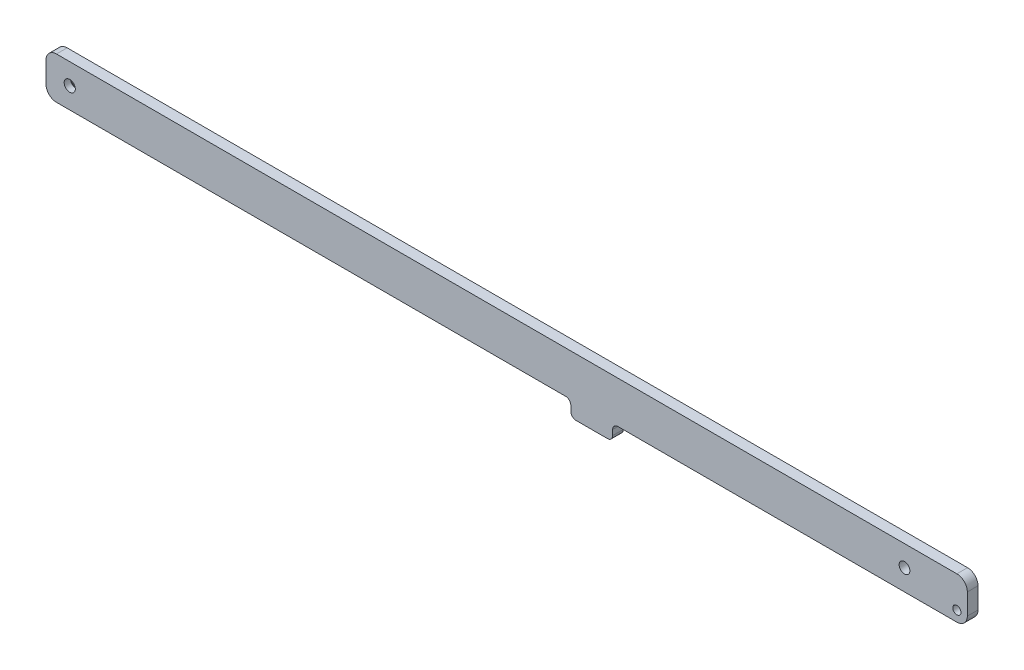
SolidWorks part; units mm, degrees
material "PC High Viscosity"
ref_plane "Front Plane" through (0, 0, 0) normal (0, 0, 1) x (1, 0, 0)
ref_plane "Top Plane" through (0, 0, 0) normal (0, 1, 0) x (1, 0, 0)
ref_plane "Right Plane" through (0, 0, 0) normal (1, 0, 0) x (0, 0, -1)
sketch "Sketch1" plane through (0, 0, 0) normal (0, 0, 1) x (1, 0, 0)
  line L1 (0, 0) -> (40.5308, 0)
  line L2 (0, 0) -> (0, 25.4)
  line L3 (0, 25.4) -> (40.5307, 25.4)
  line L4 (558.8, 0) -> (558.8, 25.4)
  line L11 (558.8, 10.0162) -> (552.45, 13.6823) construction
  line L12 (552.45, 13.6823) -> (546.1, 10.0162) construction
  line L13 (546.1, 10.0162) -> (546.1, 2.6838) construction
  line L14 (546.1, 2.6838) -> (552.45, -0.9823) construction
  line L15 (552.45, -0.9823) -> (558.8, 2.6838) construction
  line L16 (558.8, 2.6838) -> (558.8, 10.0162) construction
  line L19 (318.3103, 0) -> (318.3103, -9.525)
  line L20 (318.3103, -9.525) -> (343.7103, -9.525)
  line L21 (343.7103, -9.525) -> (343.7103, 0)
  line L22 (40.5307, 25.4) -> (558.8, 25.4)
  line L23 (40.5308, 0) -> (318.3103, 0)
  line L24 (343.7103, 0) -> (558.8, 0)
  circle A0 centre (552.45, 6.35) radius 2.4892
  circle A1 centre (552.45, 6.35) radius 6.35 construction
  dimension "D5" = 4.9784
  dimension "D7" = 12.7
  dimension "D1" = 558.8
  dimension "D2" = 25.4
  dimension "D3" = 9.525
  dimension "D4" = 318.3103
  dimension "D9" = 25.4
extrude "Boss-Extrude1" add sketch "Sketch1" along normal blind 6.477 contours L3 | L1 L4 L3 L2 A0 | L1 region at (279.8974, 12.4155, 0)
fillet "Fillet2" radius 6.35 4 edges at (558.8, 25.4, 3.2385) (0, 0, 3.2385) (0, 25.4, 3.2385) (558.8, 0, 3.2385)
sketch "Sketch2" plane through (0, 0, 6.477) normal (0, 0, 1) x (1, 0, 0)
  line L2 (558.8, 6.35) -> (558.8, 19.05) construction
  line L3 (6.35, 25.4) -> (552.45, 25.4) construction
  circle A0 centre (520.7, 12.7) radius 3.2639
  dimension "D1" = 6.5278
  dimension "D2" = 12.7
  dimension "D3" = 38.1
mirror "Mirror2" about plane through (0, 0, 0) normal (0, 0, 1) of bodies 101 108
delete or keep bodies "Body-Delete/Keep 1" type delete bodies bodies 101
fillet "Fillet3" radius 3.175 4 edges at (343.7103, 0, -3.2385) (343.7103, -9.525, -3.2385) (318.3103, -9.525, -3.2385) (318.3103, 0, -3.2385)
extrude "Cut-Extrude1" cut sketch "Sketch2" against normal through all
hole_wizard "CSK for 1/4 Flat Head Machine Screw (100)1" positions "Sketch3" profile "Sketch4" countersink size "1/4" standard "ANSI Inch"
sketch "Sketch3" plane through (0, 0, -6.477) normal (0, 0, 1) x (1, 0, 0)
  line L0 (6.35, 0) -> (315.1353, 0) construction
  line L1 (0, 6.35) -> (0, 19.05) construction
  point P0 (14.3939, 12.7)
  dimension "D1" = 12.7
  dimension "D2" = 14.3939
sketch "Sketch4" plane through (14.3939, 12.7, -6.477) normal (1, 0, 0) x (0, 1, 0)
  line L0 (0, 0) -> (0, 21.0798)
  line L1 (0, 21.0798) -> (3.3782, 19.05)
  line L2 (3.3782, 19.05) -> (3.3782, 2.5682)
  line L3 (3.3782, 2.5682) -> (6.4389, 0)
  line L5 (6.4389, 0) -> (0, 0)
  line L6 (-3.3782, 2.5682) -> (-6.4389, 0) construction
  line L10 (0, 21.0798) -> (-3.3782, 19.05) construction
  line L11 (0, -6.35) -> (0, 107.95) construction
  dimension "Hole Dia." = 6.7564
  dimension "Hole Depth" = 19.05
  dimension "Near C'Sink Dia." = 12.8778
  dimension "Near C'Sink Angle" = 100
  dimension "Drill Angle" = 118
